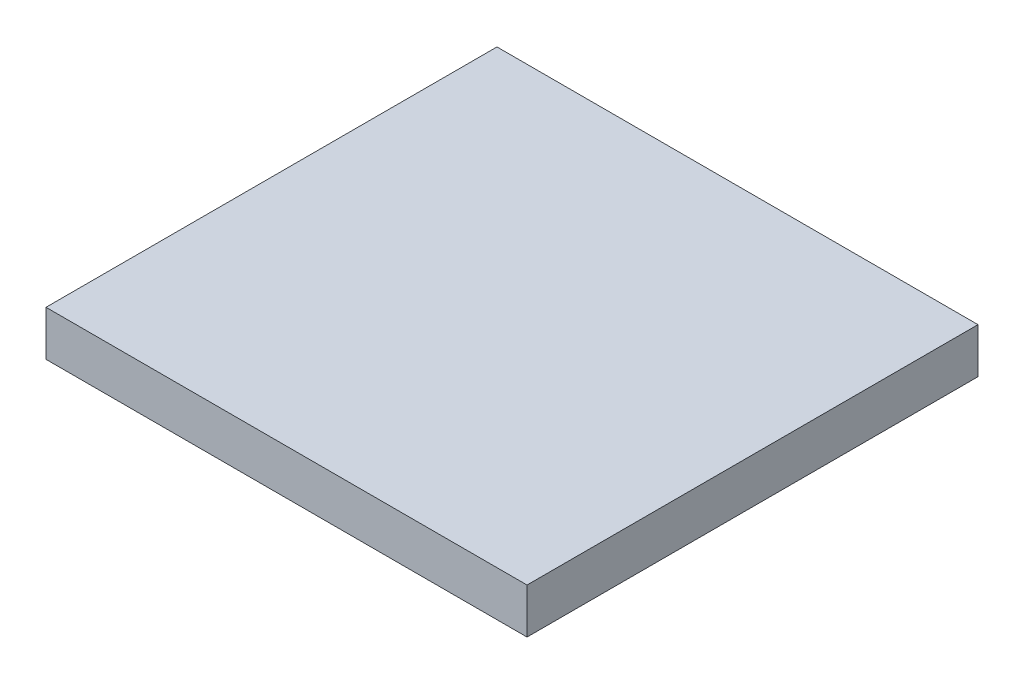
SolidWorks part; units mm, degrees
ref_plane "Front Plane" through (0, 0, 0) normal (0, 0, 1) x (1, 0, 0)
ref_plane "Top Plane" through (0, 0, 0) normal (0, 1, 0) x (1, 0, 0)
ref_plane "Right Plane" through (0, 0, 0) normal (1, 0, 0) x (0, 0, -1)
sketch "Sketch1" plane through (0, 0, 0) normal (0, 1, 0) x (1, 0, 0)
  line L1 (-8, -7.5) -> (8, -7.5)
  line L2 (-8, -7.5) -> (-8, 7.5)
  line L3 (-8, 7.5) -> (8, 7.5)
  line L4 (8, -7.5) -> (8, 7.5)
  line L5 (-8, -7.5) -> (8, 7.5) construction
  line L6 (-8, 7.5) -> (8, -7.5) construction
  point P0 (0, 0)
  dimension "D1" = 16
  dimension "D2" = 15
extrude "Boss-Extrude1" add sketch "Sketch1" along normal blind 1.5
